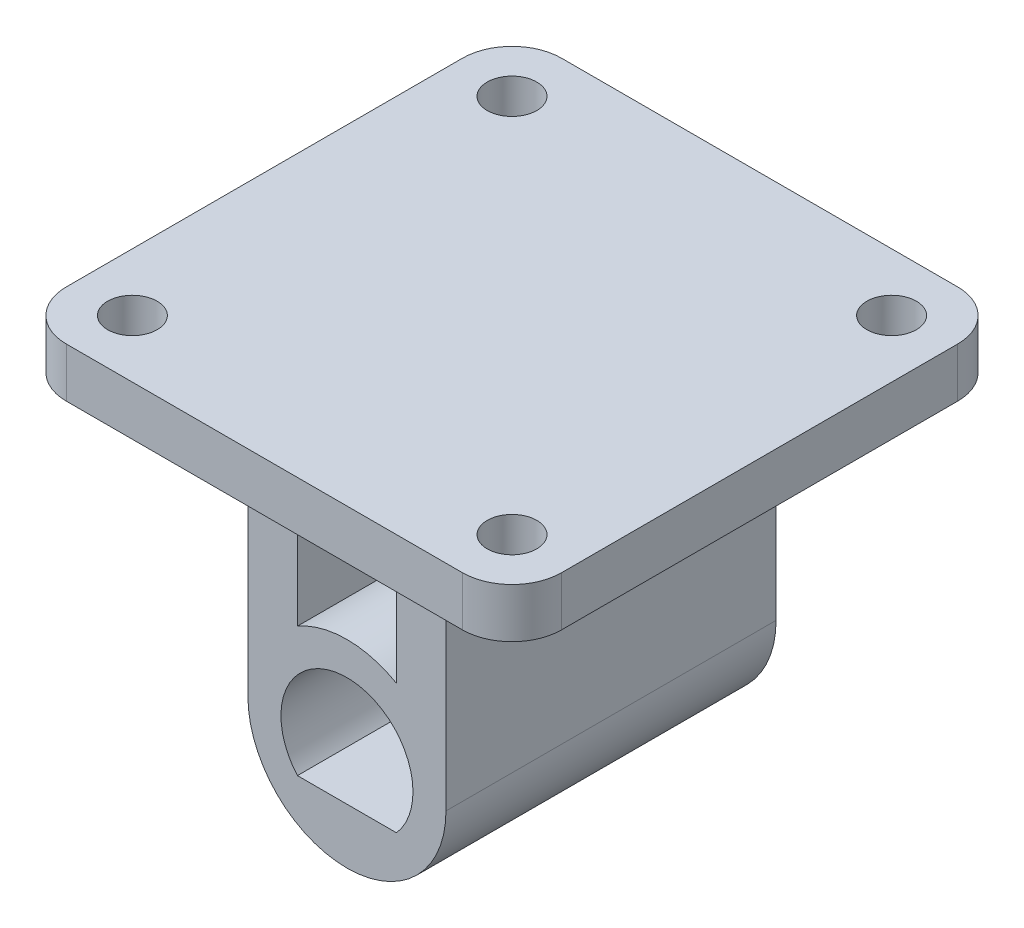
SolidWorks part; units mm, degrees
ref_plane "Alzado" through (0, 0, 0) normal (0, 0, 1) x (1, 0, 0)
ref_plane "Planta" through (0, 0, 0) normal (0, 1, 0) x (1, 0, 0)
ref_plane "Vista lateral" through (0, 0, 0) normal (1, 0, 0) x (0, 0, -1)
sketch "Croquis1" plane through (0, 0, 0) normal (0, 1, 0) x (1, 0, 0)
  line L0 (0, 0) -> (8.5714, 0) construction
  line L1 (0, 0) -> (0, -8.3442) construction
  line L2 (-15, 15) -> (15, 15)
  line L3 (15, 15) -> (15, -15)
  line L4 (15, -15) -> (-15, -15)
  line L5 (-15, -15) -> (-15, 15)
  dimension "D1" = 30
  dimension "D2" = 30
extrude "Saliente-Extruir1" add sketch "Croquis1" along normal blind 3
ref_plane "Plano1" through (0, 0, 10) normal (0, 0, 1) x (1, 0, 0)
sketch "Croquis3" plane through (0, 0, 10) normal (0, 0, 1) x (1, 0, 0)
  line L0 (0, 0) -> (0, 4.8812) construction
  line L5 (0, 0) -> (0, -9.5797) construction
  line L6 (-3, 0) -> (-3, -9.8038)
  line L11 (-6, 0) -> (-6, -15)
  line L12 (-15, 0) -> (15, 0) construction
  line L13 (6, -15) -> (6, 0)
  line L14 (6, 0) -> (3, 0)
  line L17 (-3, 0) -> (-6, 0)
  line L19 (3, -9.8038) -> (3, 0)
  line L20 (-3, -17.6458) -> (3, -17.6458)
  arc A2 (-6, -15) -> (6, -15) centre (0, -15) ccw
  arc A8 (-3, -9.8038) -> (3, -9.8038) centre (0, -15) cw
  arc A9 (3, -17.6458) -> (-3, -17.6458) centre (0, -15) ccw
  dimension "D1" = 6
  dimension "D3" = 15
  dimension "D5" = 6
  dimension "D4" = 6
  dimension "D8" = 3
  dimension "D6" = 6
  dimension "D2" = 4
  dimension "D7" = 6
extrude "Saliente-Extruir2" add sketch "Croquis3" against normal blind 20
sketch "Croquis4" plane through (0, 3, 0) normal (0, 1, 0) x (1, 0, 0)
  line L0 (0, 0) -> (-3.4922, 0) construction
  line L1 (0, 0) -> (0, 4.1707) construction
  circle A0 centre (-11.5, 11.5) radius 1.5
  circle A1 centre (11.5, 11.5) radius 1.5
  circle A2 centre (11.5, -11.5) radius 1.5
  circle A3 centre (-11.5, -11.5) radius 1.5
  dimension "D1" = 3
  dimension "D2" = 3
  dimension "D3" = 3
  dimension "D4" = 3
  dimension "D5" = 23
  dimension "D6" = 23
extrude "Cortar-Extruir1" cut sketch "Croquis4" against normal through all
fillet "Redondeo2" radius 3 4 edges at (15, 1.5, -15) (-15, 1.5, -15) (15, 1.5, 15) (-15, 1.5, 15)
fillet "Redondeo4" radius 2 2 edges at (-3, 0, 0) (3, 0, 0)
fillet "Redondeo5" radius 3 6 edges at (3.5, 0, -10) (-3.5, 0, -10) (-3.5, 0, 10) (3.5, 0, 10) (6, 0, 0) (-6, 0, 0)
